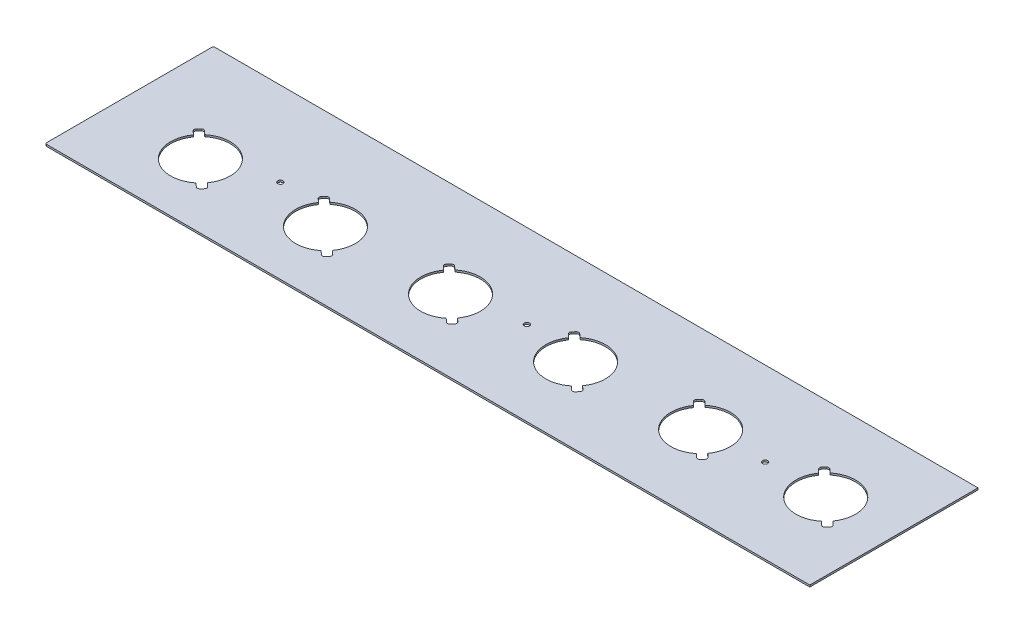
SolidWorks part; units mm, degrees
material "E-Glass Fiber"
ref_plane "Front" through (0, 0, 0) normal (0, 0, 1) x (1, 0, 0)
ref_plane "Top" through (0, 0, 0) normal (0, 1, 0) x (1, 0, 0)
ref_plane "Right" through (0, 0, 0) normal (1, 0, 0) x (0, 0, -1)
sketch "Sketch2" plane through (0, 0, 0) normal (0, 1, 0) x (1, 0, 0)
  line L1 (-317.5, 69.85) -> (317.5, 69.85)
  line L2 (-317.5, 69.85) -> (-317.5, -69.85)
  line L3 (-317.5, -69.85) -> (317.5, -69.85)
  line L5 (317.5, 69.85) -> (317.5, -69.85)
  line L6 (-317.5, 69.85) -> (317.5, -69.85) construction
  line L13 (180.6831, -17.7651) -> (183.4195, -20.3292) construction
  line L14 (183.5114, -23.1562) -> (181.6653, -25.1264) construction
  line L18 (178.8384, -25.2183) -> (176.102, -22.6542) construction
  line L19 (141.7903, 18.6785) -> (144.5267, 16.1144) construction
  line L20 (139.9455, 11.2254) -> (137.2091, 13.7894) construction
  line L24 (137.1172, 16.6164) -> (138.9634, 18.5866) construction
  line L25 (180.4727, -17.5679) -> (183.4195, -20.3292)
  line L30 (183.5114, -23.1562) -> (181.6653, -25.1264)
  line L31 (178.8384, -25.2183) -> (175.8915, -22.457)
  line L32 (141.7903, 18.6785) -> (144.7372, 15.9172)
  line L36 (140.156, 11.0281) -> (137.2091, 13.7894)
  line L37 (137.1172, 16.6164) -> (138.9634, 18.5866)
  line L38 (39.3639, 7.9555) -> (36.6275, 10.5195) construction
  line L42 (242.372, 21.9484) -> (245.1084, 19.3843) construction
  line L43 (237.6989, 19.8863) -> (239.545, 21.8565) construction
  line L44 (240.5272, 14.4952) -> (237.7908, 17.0593) construction
  line L45 (242.372, 21.9484) -> (245.3189, 19.1871)
  line L46 (237.6989, 19.8863) -> (239.545, 21.8565)
  line L47 (240.7377, 14.298) -> (237.7908, 17.0593)
  line L48 (281.2648, -14.4952) -> (284.0012, -17.0593) construction
  line L49 (284.0931, -19.8863) -> (282.247, -21.8565) construction
  line L50 (279.42, -21.9484) -> (276.6836, -19.3843) construction
  line L51 (281.0543, -14.298) -> (284.0012, -17.0593)
  line L52 (284.0931, -19.8863) -> (282.247, -21.8565)
  line L53 (279.42, -21.9484) -> (276.4731, -19.1871)
  line L78 (36.5356, 13.3465) -> (38.3817, 15.3167) construction
  line L79 (41.2086, 15.4086) -> (43.9451, 12.8445) construction
  line L80 (80.1015, -21.035) -> (82.8379, -23.5991) construction
  line L81 (82.9298, -26.4261) -> (81.0836, -28.3963) construction
  line L82 (78.2567, -28.4882) -> (75.5203, -25.9241) construction
  line L83 (39.5744, 7.7582) -> (36.6275, 10.5195)
  line L84 (36.5356, 13.3465) -> (38.3817, 15.3167)
  line L85 (41.2086, 15.4086) -> (44.1555, 12.6473)
  line L86 (79.891, -20.8378) -> (82.8379, -23.5991)
  line L87 (82.9298, -26.4261) -> (81.0836, -28.3963)
  line L88 (78.2567, -28.4882) -> (75.3098, -25.7269)
  line L89 (-61.2178, 4.6856) -> (-63.9542, 7.2496) construction
  line L90 (-64.0461, 10.0766) -> (-62.1999, 12.0468) construction
  line L91 (-59.373, 12.1387) -> (-56.6366, 9.5746) construction
  line L92 (-20.4802, -24.3049) -> (-17.7438, -26.869) construction
  line L93 (-17.6519, -29.696) -> (-19.498, -31.6662) construction
  line L94 (-22.325, -31.7581) -> (-25.0614, -29.194) construction
  line L95 (-61.0073, 4.4883) -> (-63.9542, 7.2496)
  line L96 (-64.0461, 10.0766) -> (-62.1999, 12.0468)
  line L97 (-59.373, 12.1387) -> (-56.4261, 9.3774)
  line L98 (-20.6907, -24.1077) -> (-17.7438, -26.869)
  line L99 (-17.6519, -29.696) -> (-19.498, -31.6662)
  line L100 (-22.325, -31.7581) -> (-25.2718, -28.9968)
  line L101 (-161.7994, 1.4157) -> (-164.5359, 3.9798) construction
  line L102 (-164.6278, 6.8067) -> (-162.7816, 8.7769) construction
  line L103 (-159.9547, 8.8688) -> (-157.2183, 6.3047) construction
  line L104 (-121.0619, -27.5748) -> (-118.3254, -30.1389) construction
  line L105 (-118.2335, -32.9659) -> (-120.0797, -34.9361) construction
  line L106 (-122.9066, -35.028) -> (-125.643, -32.4639) construction
  line L107 (-161.589, 1.2184) -> (-164.5359, 3.9798)
  line L108 (-164.6278, 6.8067) -> (-162.7816, 8.7769)
  line L109 (-159.9547, 8.8688) -> (-157.0078, 6.1075)
  line L110 (-121.2723, -27.3776) -> (-118.3254, -30.1389)
  line L111 (-118.2335, -32.9659) -> (-120.0797, -34.9361)
  line L112 (-122.9066, -35.028) -> (-125.8535, -32.2667)
  line L113 (-221.6435, -30.8447) -> (-218.9071, -33.4088) construction
  line L114 (-218.8152, -36.2358) -> (-220.6613, -38.206) construction
  line L115 (-223.4883, -38.2979) -> (-226.2247, -35.7338) construction
  line L116 (-260.5363, 5.5989) -> (-257.7999, 3.0348) construction
  line L117 (-265.2094, 3.5368) -> (-263.3633, 5.507) construction
  line L118 (-262.3811, -1.8542) -> (-265.1175, 0.7099) construction
  line L119 (-221.854, -30.6475) -> (-218.9071, -33.4088)
  line L120 (-218.8152, -36.2358) -> (-220.6613, -38.206)
  line L121 (-223.4883, -38.2979) -> (-226.4352, -35.5366)
  line L122 (-260.5363, 5.5989) -> (-257.5895, 2.8376)
  line L123 (-265.2094, 3.5368) -> (-263.3633, 5.507)
  line L124 (-262.1706, -2.0515) -> (-265.1175, 0.7099)
  arc A16 (183.5114, -23.1562) -> (183.4195, -20.3292) centre (182.052, -21.7887) ccw construction
  arc A20 (178.8384, -25.2183) -> (181.6653, -25.1264) centre (180.2059, -23.7589) ccw construction
  arc A24 (141.7903, 18.6785) -> (138.9634, 18.5866) centre (140.4228, 17.2191) ccw construction
  arc A28 (137.1172, 16.6164) -> (137.2091, 13.7894) centre (138.5767, 15.2489) ccw construction
  arc A45 (183.5114, -23.1562) -> (183.4195, -20.3292) centre (182.052, -21.7887) ccw
  arc A46 (178.8384, -25.2183) -> (181.6653, -25.1264) centre (180.2059, -23.7589) ccw
  arc A47 (240.7377, 14.298) -> (276.4731, -19.1871) centre (260.896, 0) ccw
  arc A48 (242.372, 21.9484) -> (239.545, 21.8565) centre (241.0045, 20.489) ccw construction
  arc A49 (237.6989, 19.8863) -> (237.7908, 17.0593) centre (239.1583, 18.5188) ccw construction
  arc A50 (242.372, 21.9484) -> (239.545, 21.8565) centre (241.0045, 20.489) ccw
  arc A51 (237.6989, 19.8863) -> (237.7908, 17.0593) centre (239.1583, 18.5188) ccw
  arc A52 (284.0931, -19.8863) -> (284.0012, -17.0593) centre (282.6337, -18.5188) ccw construction
  arc A53 (279.42, -21.9484) -> (282.247, -21.8565) centre (280.7875, -20.489) ccw construction
  arc A54 (284.0931, -19.8863) -> (284.0012, -17.0593) centre (282.6337, -18.5188) ccw
  arc A55 (279.42, -21.9484) -> (282.247, -21.8565) centre (280.7875, -20.489) ccw
  arc A56 (281.0543, -14.298) -> (245.3189, 19.1871) centre (260.896, 0) ccw
  arc A79 (141.7903, 18.6785) -> (138.9634, 18.5866) centre (140.4228, 17.2191) ccw
  arc A80 (137.1172, 16.6164) -> (137.2091, 13.7894) centre (138.5767, 15.2489) ccw
  arc A81 (180.4727, -17.5679) -> (144.7372, 15.9172) centre (160.3143, -3.2699) ccw
  arc A82 (140.156, 11.0281) -> (175.8915, -22.457) centre (160.3143, -3.2699) ccw
  arc A83 (36.5356, 13.3465) -> (36.6275, 10.5195) centre (37.995, 11.979) ccw construction
  arc A84 (41.2086, 15.4086) -> (38.3817, 15.3167) centre (39.8411, 13.9492) ccw construction
  arc A85 (82.9298, -26.4261) -> (82.8379, -23.5991) centre (81.4704, -25.0586) ccw construction
  arc A86 (78.2567, -28.4882) -> (81.0836, -28.3963) centre (79.6242, -27.0288) ccw construction
  arc A87 (36.5356, 13.3465) -> (36.6275, 10.5195) centre (37.995, 11.979) ccw
  arc A88 (41.2086, 15.4086) -> (38.3817, 15.3167) centre (39.8411, 13.9492) ccw
  arc A89 (82.9298, -26.4261) -> (82.8379, -23.5991) centre (81.4704, -25.0586) ccw
  arc A90 (78.2567, -28.4882) -> (81.0836, -28.3963) centre (79.6242, -27.0288) ccw
  arc A91 (-64.0461, 10.0766) -> (-63.9542, 7.2496) centre (-62.5867, 8.7091) ccw construction
  arc A92 (-59.373, 12.1387) -> (-62.1999, 12.0468) centre (-60.7405, 10.6793) ccw construction
  arc A93 (-17.6519, -29.696) -> (-17.7438, -26.869) centre (-19.1113, -28.3285) ccw construction
  arc A94 (-22.325, -31.7581) -> (-19.498, -31.6662) centre (-20.9574, -30.2987) ccw construction
  arc A95 (-64.0461, 10.0766) -> (-63.9542, 7.2496) centre (-62.5867, 8.7091) ccw
  arc A96 (-59.373, 12.1387) -> (-62.1999, 12.0468) centre (-60.7405, 10.6793) ccw
  arc A97 (-17.6519, -29.696) -> (-17.7438, -26.869) centre (-19.1113, -28.3285) ccw
  arc A98 (-22.325, -31.7581) -> (-19.498, -31.6662) centre (-20.9574, -30.2987) ccw
  arc A99 (-164.6278, 6.8067) -> (-164.5359, 3.9798) centre (-163.1683, 5.4392) ccw construction
  arc A100 (-159.9547, 8.8688) -> (-162.7816, 8.7769) centre (-161.3222, 7.4094) ccw construction
  arc A101 (-118.2335, -32.9659) -> (-118.3254, -30.1389) centre (-119.693, -31.5983) ccw construction
  arc A102 (-122.9066, -35.028) -> (-120.0797, -34.9361) centre (-121.5391, -33.5686) ccw construction
  arc A103 (-164.6278, 6.8067) -> (-164.5359, 3.9798) centre (-163.1683, 5.4392) ccw
  arc A104 (-159.9547, 8.8688) -> (-162.7816, 8.7769) centre (-161.3222, 7.4094) ccw
  arc A105 (-118.2335, -32.9659) -> (-118.3254, -30.1389) centre (-119.693, -31.5983) ccw
  arc A106 (-122.9066, -35.028) -> (-120.0797, -34.9361) centre (-121.5391, -33.5686) ccw
  arc A107 (-218.8152, -36.2358) -> (-218.9071, -33.4088) centre (-220.2746, -34.8682) ccw construction
  arc A108 (-223.4883, -38.2979) -> (-220.6613, -38.206) centre (-222.1208, -36.8385) ccw construction
  arc A109 (-260.5363, 5.5989) -> (-263.3633, 5.507) centre (-261.9039, 4.1395) ccw construction
  arc A110 (-265.2094, 3.5368) -> (-265.1175, 0.7099) centre (-263.75, 2.1693) ccw construction
  arc A111 (-218.8152, -36.2358) -> (-218.9071, -33.4088) centre (-220.2746, -34.8682) ccw
  arc A112 (-223.4883, -38.2979) -> (-220.6613, -38.206) centre (-222.1208, -36.8385) ccw
  arc A113 (-260.5363, 5.5989) -> (-263.3633, 5.507) centre (-261.9039, 4.1395) ccw
  arc A114 (-265.2094, 3.5368) -> (-265.1175, 0.7099) centre (-263.75, 2.1693) ccw
  arc A115 (79.891, -20.8378) -> (44.1555, 12.6473) centre (59.7327, -6.5398) ccw
  arc A116 (-20.6907, -24.1077) -> (-56.4261, 9.3774) centre (-40.849, -9.8097) ccw
  arc A117 (-121.2723, -27.3776) -> (-157.0078, 6.1075) centre (-141.4306, -13.0796) ccw
  arc A118 (-221.854, -30.6475) -> (-257.5895, 2.8376) centre (-242.0123, -16.3495) ccw
  arc A119 (-262.1706, -2.0515) -> (-226.4352, -35.5366) centre (-242.0123, -16.3495) ccw
  arc A120 (-161.589, 1.2184) -> (-125.8535, -32.2667) centre (-141.4306, -13.0796) ccw
  arc A121 (-61.0073, 4.4883) -> (-25.2718, -28.9968) centre (-40.849, -9.8097) ccw
  arc A122 (39.5744, 7.7582) -> (75.3098, -25.7269) centre (59.7327, -6.5398) ccw
  point P0 (0, 0)
  dimension "D3" = 24.7142
  dimension "D1" = 635
  dimension "D2" = 139.7
extrude "Boss-Extrude1" add sketch "Sketch2" along normal blind 1.524
sketch "Sketch3" [suppressed] plane through (0, 1.524, 0) normal (0, 1, 0) x (1, 0, 0)
  line L42 (-317.5, -69.85) -> (-292.1, -69.85) construction
  line L43 (285.896, 0) -> (287.166, 0)
  line L44 (-317.5, 69.85) -> (-317.5, -69.85) construction
  line L45 (-317.5, 49.8475) -> (-317.5, 69.85) construction
  line L46 (260.896, -26.27) -> (260.896, 26.27) construction
  line L47 (-292.1, -69.85) -> (-292.1, 69.85)
  line L48 (-292.1, 49.8475) -> (-317.5, 49.8475)
  line L49 (234.626, 26.27) -> (287.166, 26.27) construction
  line L50 (-292.1, -49.8475) -> (-317.5, -49.8475)
  line L51 (-317.5, -49.8475) -> (-317.5, -69.85) construction
  line L52 (287.166, 0) -> (287.166, -26.27)
  line L53 (287.166, 0) -> (234.626, 0) construction
  line L54 (234.626, -26.27) -> (234.626, 26.27) construction
  line L55 (260.896, 26.27) -> (234.626, 26.27)
  line L57 (234.626, 26.27) -> (234.626, 0)
  line L58 (234.626, 0) -> (235.896, 0)
  line L59 (260.896, 26.27) -> (260.896, 25)
  line L61 (287.166, -26.27) -> (260.896, -26.27)
  line L63 (260.896, -26.27) -> (260.896, -25)
  line L64 (160.261, -26.27) -> (160.261, 26.27) construction
  line L65 (133.991, 26.27) -> (186.531, 26.27) construction
  line L67 (186.531, -26.27) -> (133.991, -26.27) construction
  line L68 (186.531, 0) -> (133.991, 0) construction
  line L69 (133.991, -26.27) -> (133.991, 26.27) construction
  line L70 (160.261, 26.27) -> (133.991, 26.27)
  line L71 (133.991, 26.27) -> (133.991, 0)
  line L72 (133.991, 0) -> (135.261, 0)
  line L73 (160.261, 26.27) -> (160.261, 25)
  line L74 (185.261, 0) -> (186.531, 0)
  line L75 (186.531, 0) -> (186.531, -26.27)
  line L76 (186.531, -26.27) -> (160.261, -26.27)
  line L77 (160.261, -26.27) -> (160.261, -25)
  line L78 (59.626, -26.27) -> (59.626, 26.27) construction
  line L79 (33.356, 26.27) -> (85.896, 26.27) construction
  line L81 (85.896, -26.27) -> (33.356, -26.27) construction
  line L82 (85.896, 0) -> (33.356, 0) construction
  line L83 (33.356, -26.27) -> (33.356, 26.27) construction
  line L85 (59.626, 25) -> (59.626, 26.27)
  line L86 (59.626, 26.27) -> (33.356, 26.27)
  line L87 (33.356, 26.27) -> (33.356, 0)
  line L88 (33.356, 0) -> (34.626, 0)
  line L90 (84.626, 0) -> (85.896, 0)
  line L92 (85.896, 0) -> (85.896, -26.27)
  line L93 (85.896, -26.27) -> (59.626, -26.27)
  line L94 (59.626, -26.27) -> (59.626, -25)
  line L96 (-292.1, 49.5863) -> (-292.1, 88.9) construction
  line L97 (317.5, 69.85) -> (-317.5, 69.85) construction
  line L98 (-317.5, -69.85) -> (317.5, -69.85) construction
  line L99 (317.5, 69.85) -> (-317.5, 69.85) construction
  arc A24 (241.009, 15.1494) -> (276.0454, -19.887) centre (260.896, 0) ccw construction
  arc A25 (280.783, -15.1494) -> (245.7466, 19.887) centre (260.896, 0) ccw construction
  arc A26 (140.374, 15.1494) -> (175.4104, -19.887) centre (160.261, 0) ccw construction
  arc A27 (180.148, -15.1494) -> (145.1116, 19.887) centre (160.261, 0) ccw construction
  point P8 (260.896, 0)
  point P16 (160.261, 0)
  point P17 (260.896, 0)
  point P37 (160.261, 0)
  point P52 (59.626, 0)
  point P60 (59.626, 0)
  dimension "D1" = 20.0025
fillet "Fillet1" radius 1.27 2 edges at (-317.5, 0.762, 69.85) (-317.5, 0.762, -69.85)
hole_wizard "#8 Clearance Hole1" positions "Sketch4" profile "Sketch5" hole size "#8" standard "ANSI Inch" end condition through all
sketch "Sketch4" plane through (0, 1.524, 0) normal (0, 1, 0) x (1, 0, 0)
  point P0 (210.5786, 0)
  point P3 (12.7, 0)
  point P6 (-191.9606, 0)
sketch "Sketch5" plane through (210.5786, 1.524, 0) normal (1, 0, 0) x (0, 0, 1)
  line L0 (0, 0) -> (0, 1.524)
  line L1 (0, 1.524) -> (2.1526, 1.524)
  line L2 (2.1526, 1.524) -> (2.1526, 0)
  line L5 (2.1526, 0) -> (0, 0)
  line L11 (0, -6.35) -> (0, 107.95) construction
  dimension "Thru Hole Dia." = 4.3053
  dimension "Thru Hole Depth" = 1.524
